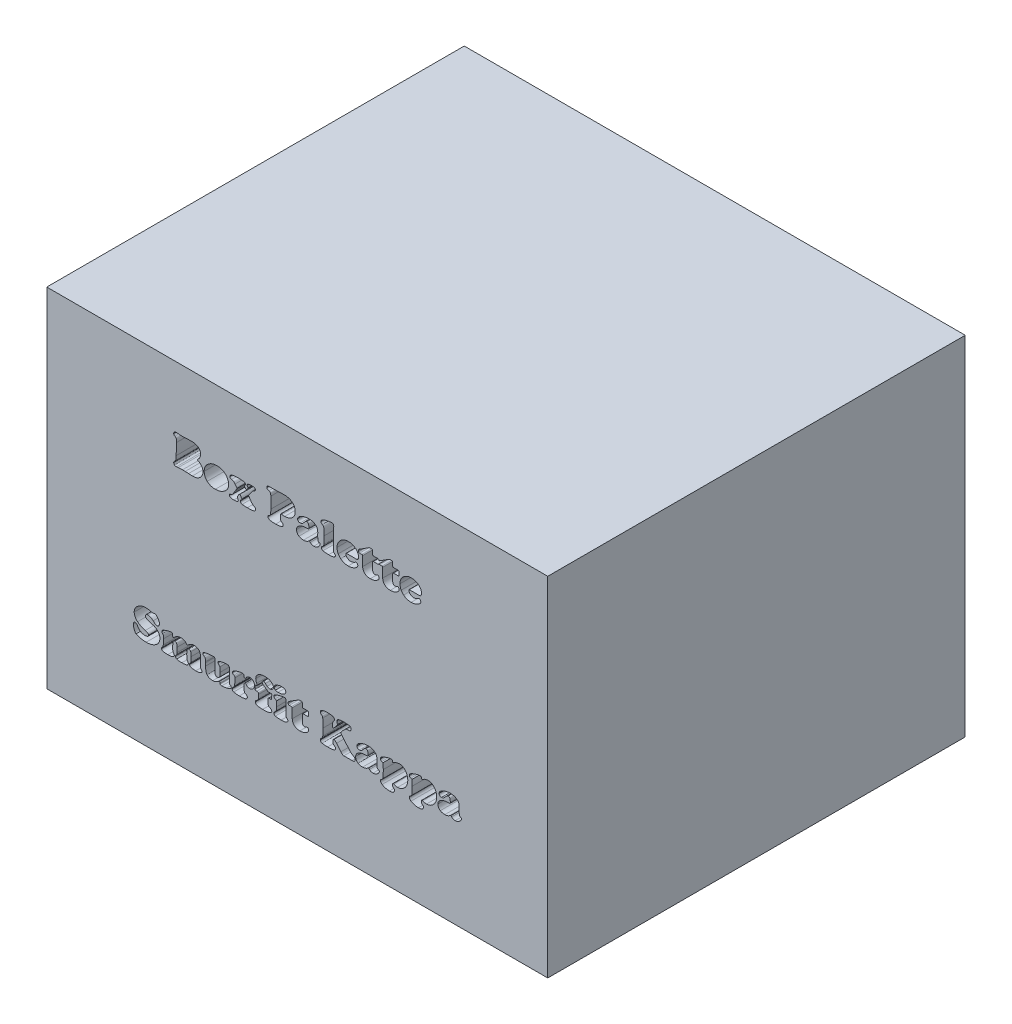
SolidWorks part; units mm, degrees
material "Eau"
ref_plane "Plan de face" through (0, 0, 0) normal (0, 0, 1) x (1, 0, 0)
ref_plane "Plan de dessus" through (0, 0, 0) normal (0, 1, 0) x (1, 0, 0)
ref_plane "Plan de droite" through (0, 0, 0) normal (1, 0, 0) x (0, 0, -1)
sketch "Esquisse1" plane through (0, 0, 0) normal (0, 1, 0) x (1, 0, 0)
  line L1 (-600, -500) -> (600, -500)
  line L2 (-600, -500) -> (-600, 500)
  line L3 (-600, 500) -> (600, 500)
  line L4 (600, -500) -> (600, 500)
  line L5 (-600, -500) -> (600, 500) construction
  line L6 (-600, 500) -> (600, -500) construction
  point P1 (0, 0)
  dimension "D1" = 1200
  dimension "D2" = 1000
extrude "Boss.-Extru.1" add sketch "Esquisse1" along normal mid plane 833.33
sketch "Esquisse2" plane through (0, 0, 500) normal (0, 0, 1) x (1, 0, 0)
  line L0 (-440, 200) -> (440, 200) construction
  line L1 (-600, 416.665) -> (-600, -416.665) construction
  line L2 (-440, -200) -> (440, -200) construction
  line L3 (600, 416.665) -> (600, -416.665) construction
  text T0 "Box Palette" font "Cooper Black" height in points 300
  text T1 "Smurfit Kappa" font "Cooper Black" height in points 300
  dimension "D1" = 200
  dimension "D2" = 200
  dimension "D3" = 160
  dimension "D4" = 160
  dimension "D5" = 160
  dimension "D6" = 160
extrude "Enlèv. mat.-Extru.2" cut sketch "Esquisse2" against normal through all body kept at (-600, -416.665, 500)
sketch "Esquisse3" plane through (0, -416.665, 0) normal (0, -1, 0) x (-1, 0, 0)
  point P0 (0, 0)
